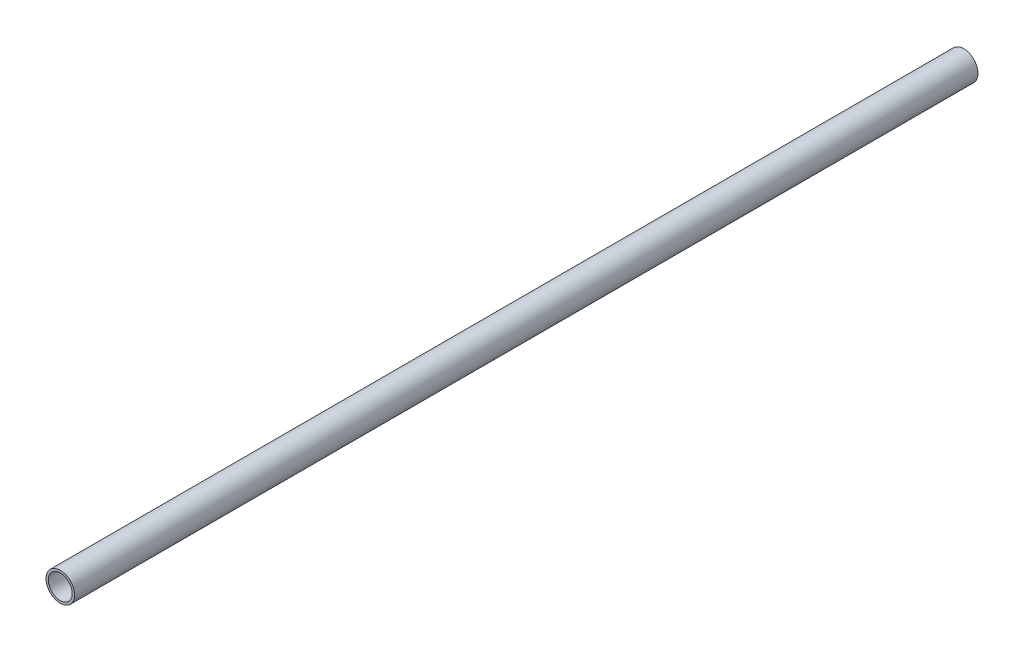
SolidWorks part; units mm, degrees
material "PVC Rigid"
ref_plane "Front Plane" through (0, 0, 0) normal (0, 0, 1) x (1, 0, 0)
ref_plane "Top Plane" through (0, 0, 0) normal (0, 1, 0) x (1, 0, 0)
ref_plane "Right Plane" through (0, 0, 0) normal (1, 0, 0) x (0, 0, -1)
sketch "Sketch1" plane through (0, 0, 0) normal (0, 0, 1) x (1, 0, 0)
  circle A0 centre (0, 0) radius 20.193
  circle A1 centre (0, 0) radius 24.13
  dimension "D1" = 48.26
  dimension "D2" = 40.386
extrude "Boss-Extrude1" add sketch "Sketch1" along normal blind 1524
ref_axis "Axis1" through (0, 0, 1524) along (0, 0, -1)
